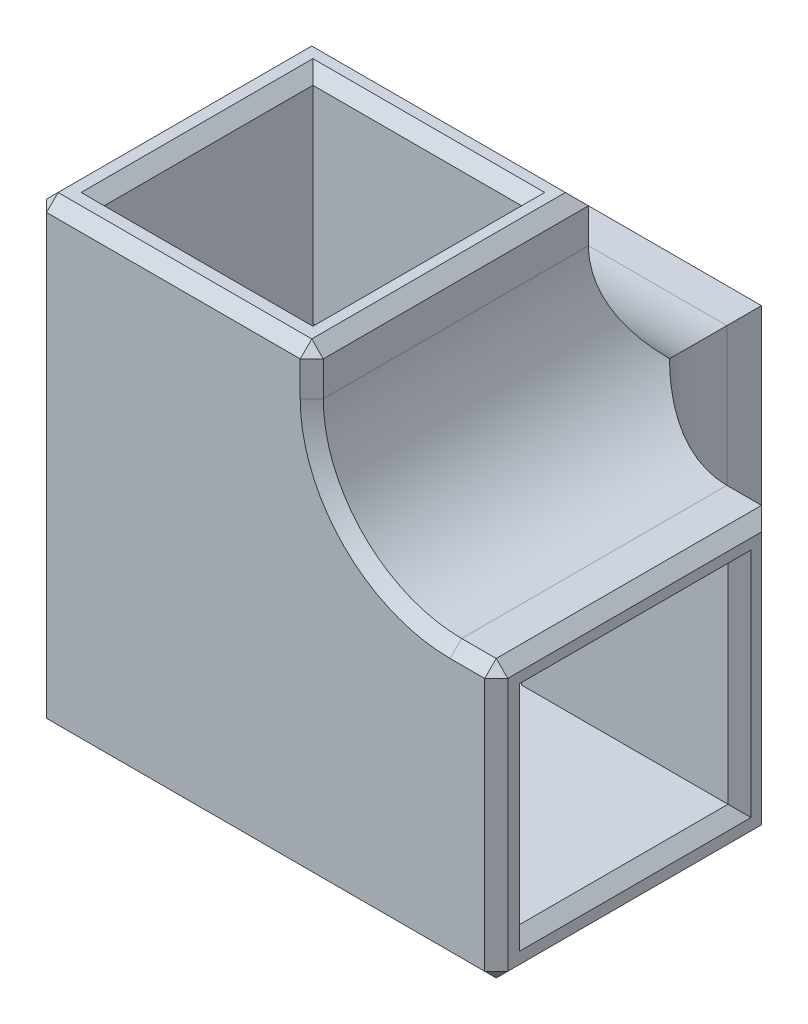
SolidWorks part; units mm, degrees
ref_plane "Front Plane" through (0, 0, 0) normal (0, 0, 1) x (1, 0, 0)
ref_plane "Top Plane" through (0, 0, 0) normal (0, 1, 0) x (1, 0, 0)
ref_plane "Right Plane" through (0, 0, 0) normal (1, 0, 0) x (0, 0, -1)
sketch "Sketch1" plane through (0, 0, 0) normal (0, 1, 0) x (1, 0, 0)
  line L0 (0, 0) -> (0, 36.7946) construction
  line L1 (0, 0) -> (54.9405, 0) construction
  line L2 (-12, 28) -> (-12, -12)
  line L3 (-12, -12) -> (28, -12)
  line L4 (28, -12) -> (28, 12)
  line L5 (28, 12) -> (12, 12)
  line L6 (12, 12) -> (12, 28)
  line L7 (12, 28) -> (-12, 28)
  dimension "D1" = 12
  dimension "D2" = 12
  dimension "D3" = 24
  dimension "D4" = 24
  dimension "D5" = 40
  dimension "D6" = 40
extrude "Boss-Extrude1" add sketch "Sketch1" along normal blind 24
sketch "Sketch2" plane through (0, 24, 0) normal (0, 1, 0) x (1, 0, 0)
  line L1 (-12, -12) -> (12, -12)
  line L2 (-12, -12) -> (-12, 12)
  line L3 (-12, 12) -> (12, 12)
  line L4 (12, -12) -> (12, 12)
extrude "Boss-Extrude2" add sketch "Sketch2" along normal blind 16
fillet "Fillet1" radius 12 1 edges at (12, 24, 0)
fillet "Fillet2" radius 12 2 edges at (12, 12, -12) (0, 24, -12)
sketch "Sketch3" plane through (28, 0, 0) normal (1, 0, 0) x (0, 0, -1)
  line L0 (-12, 24) -> (-12, 0) construction
  line L1 (-9, 3) -> (9.1, 3)
  line L2 (-9, 3) -> (-9, 21.1)
  line L3 (-9, 21.1) -> (9.1, 21.1)
  line L4 (9.1, 3) -> (9.1, 21.1)
  line L5 (-9, 3) -> (9.1, 21.1) construction
  line L6 (-9, 21.1) -> (9.1, 3) construction
  line L7 (-12, 0) -> (12, 0) construction
  point P0 (0.05, 12.05)
  dimension "D1" = 18.1
  dimension "D2" = 18.1
  dimension "D3" = 3
  dimension "D4" = 3
extrude "Cut-Extrude1" cut sketch "Sketch3" against normal blind 37
sketch "Sketch4" plane through (0, 40, 0) normal (0, 1, 0) x (1, 0, 0)
  line L0 (-12, 12) -> (-12, -12) construction
  line L1 (-9, -9) -> (9.1, -9)
  line L2 (-9, -9) -> (-9, 9.1)
  line L3 (-9, 9.1) -> (9.1, 9.1)
  line L4 (9.1, -9) -> (9.1, 9.1)
  line L5 (-9, -9) -> (9.1, 9.1) construction
  line L6 (-9, 9.1) -> (9.1, -9) construction
  line L7 (-12, -12) -> (12, -12) construction
  point P0 (0.05, 0.05)
  dimension "D1" = 3
  dimension "D2" = 3
  dimension "D3" = 18.1
  dimension "D4" = 18.1
extrude "Cut-Extrude2" cut sketch "Sketch4" against normal blind 37
sketch "Sketch5" plane through (0, 0, -28) normal (0, 0, -1) x (-1, 0, 0)
  line L0 (12, 24) -> (12, 0) construction
  line L1 (-9.1, 21.1) -> (9, 21.1)
  line L2 (-9.1, 21.1) -> (-9.1, 3)
  line L3 (-9.1, 3) -> (9, 3)
  line L4 (9, 21.1) -> (9, 3)
  line L5 (-9.1, 21.1) -> (9, 3) construction
  line L6 (-9.1, 3) -> (9, 21.1) construction
  line L7 (-12, 0) -> (12, 0) construction
  point P0 (-0.05, 12.05)
  dimension "D1" = 3
  dimension "D2" = 3
  dimension "D3" = 18.1
  dimension "D4" = 18.1
extrude "Cut-Extrude3" cut sketch "Sketch5" against normal blind 37
chamfer "Chamfer1" distance 1 angle 45 36 edges at (28, 12.05, 9) (28, 3, -0.05) (28, 12.05, -9.1) (28, 21.1, -0.05) (-9, 40, -0.05) (0.05, 40, 9) (9.1, 40, -0.05) (0.05, 40, -9.1) (28, 24, 0) (28, 12, -12) (0, 40, -12) (12, 40, 0) (0, 40, 12) (12, 38, 12) (15.5147, 27.5147, 12) (26, 24, 12) (28, 12, 12) (8, 0, 12) (28, 0, 0) (26, 0, -12) (15.5147, 0, -15.5147) (12, 0, -26) (-12, 24, -26) (-12, 27.5147, -15.5147) (-12, 38, -12) (-12, 40, 0) (-12, 20, 12) (-12, 0, -8) (12, 12, -28) (0, 24, -28) (-12, 12, -28) (0, 0, -28) (9.1, 12.05, -28) (0.05, 3, -28) (-9, 12.05, -28) (0.05, 21.1, -28)
